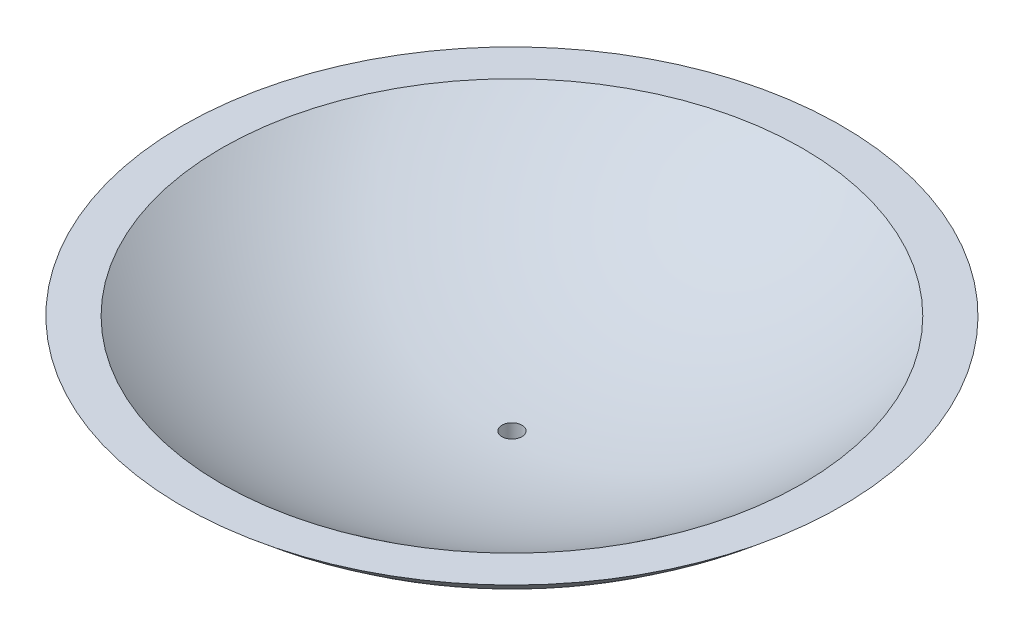
SolidWorks part; units mm, degrees
ref_plane "Front Plane" through (0, 0, 0) normal (0, 0, 1) x (1, 0, 0)
ref_plane "Top Plane" through (0, 0, 0) normal (0, 1, 0) x (1, 0, 0)
ref_plane "Right Plane" through (0, 0, 0) normal (1, 0, 0) x (0, 0, -1)
sketch "Sketch1" plane through (0, 0, 0) normal (0, 0, 1) x (1, 0, 0)
  line L0 (0, 0) -> (-12.7, 0)
  line L1 (-12.7, 0) -> (-12.7, 6.35)
  line L2 (-84.0026, 37.4634) -> (-74.0531, 37.4634)
  line L3 (0, 25.8108) -> (0, -14.8756) construction
  line L4 (0, 0) -> (0, 12.0634)
  arc A0 (-12.7, 6.35) -> (-84.0026, 37.4634) centre (0, 132.7134) cw
  arc A1 (-74.0531, 37.4634) -> (0, 12.0634) centre (0, 132.7134) ccw
  dimension "D1" = 120.65
  dimension "D3" = 6.35
  dimension "D2" = 6.35
  dimension "D4" = 12.7
  dimension "D5" = 25.4
revolve "Revolve1" add sketch "Sketch1" angle 360 about L3
hole_wizard "1/4-20 Tapped Hole1" positions "Sketch2" profile "Sketch3" tap size "1/4-20" standard "ANSI Inch"
sketch "Sketch2" plane through (0, 0, 0) normal (0, -1, 0) x (-1, 0, 0)
  point P0 (0, 0)
sketch "Sketch3" plane through (0, 0, 0) normal (1, 0, 0) x (0, 0, -1)
  line L0 (0, 0) -> (0, 14.2338)
  line L1 (0, 14.2338) -> (2.5527, 12.7)
  line L2 (2.5527, 12.7) -> (2.5527, 0)
  line L5 (2.5527, 0) -> (0, 0)
  line L10 (0, 14.2338) -> (-2.5527, 12.7) construction
  line L11 (0, -6.35) -> (0, 107.95) construction
  dimension "Tap Drill Dia." = 5.1054
  dimension "Tap Drill Depth" = 12.7
  dimension "Drill Angle" = 118
cosmetic thread "Hole Thread1" parameters "D1"=12.7, "D2"=6.35
